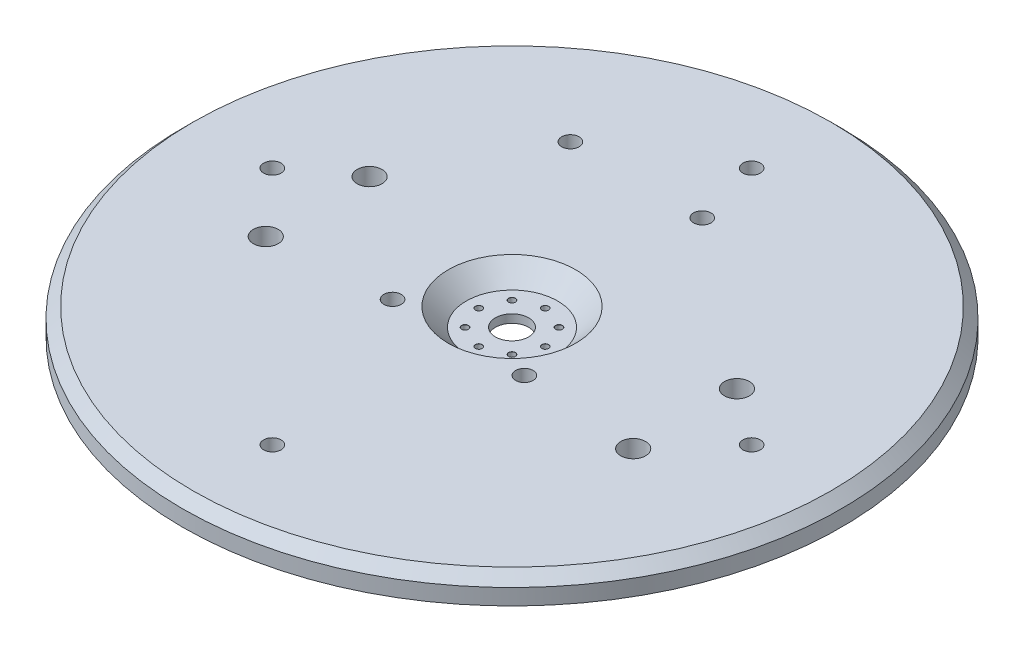
SolidWorks part; units mm, degrees
other "Markup1"
sketch "Sketch21" plane through (-65.5, -15.05, -60) normal (-0.0927, -0.2854, -0.9539) x (0.9951, -0.0609, -0.0785)
material "6061 Alloy"
ref_plane "Front Plane" through (0, 0, 0) normal (0, 0, 1) x (1, 0, 0)
ref_plane "Top Plane" through (0, 0, 0) normal (0, 1, 0) x (1, 0, 0)
ref_plane "Right Plane" through (0, 0, 0) normal (1, 0, 0) x (0, 0, -1)
sketch "Sketch1" plane through (0, 0, 0) normal (0, 1, 0) x (1, 0, 0)
  circle A0 centre (0, 0) radius 79.375
  dimension "D1" = 158.75
extrude "Boss-Extrude1" add sketch "Sketch1" along normal mid plane 6.35
sketch "Sketch2" plane through (0, -3.175, 0) normal (0, -1, 0) x (1, 0, 0)
  circle A0 centre (0, 0) radius 12.065
  circle A1 centre (0, 0) radius 79.375 construction
  dimension "D1" = 24.13
sketch "Sketch5" plane through (0, 3.175, 0) normal (0, 1, 0) x (1, 0, 0)
  circle A0 centre (0, 0) radius 10.4
  circle A1 centre (0, 0) radius 79.375 construction
  dimension "D1" = 20.8
hole_wizard "Tap Drill for M5x0.8 Tap1" positions "Sketch22" profile "Sketch23" hole size "M5x0.8" standard "ANSI Metric" end condition through all
sketch "Sketch22" plane through (0, 3.175, 0) normal (0, 1, 0) x (1, 0, 0)
  point P0 (-27.3188, 41.3898)
  point P3 (4.4312, 41.3898)
  point P6 (-15.875, -12.8959)
  point P9 (15.875, -12.8959)
  dimension "D1" = 31.75
  dimension "D2" = 41.3898
  dimension "D3" = 4.4312
  dimension "D4" = 31.75
  dimension "D5" = 12.8959
  dimension "D6" = 15.875
sketch "Sketch23" plane through (-27.3188, 3.175, -41.3898) normal (1, 0, 0) x (0, 0, 1)
  line L0 (0, 0) -> (0, 6.35)
  line L1 (0, 6.35) -> (2.1, 6.35)
  line L2 (2.1, 6.35) -> (2.1, 0)
  line L5 (2.1, 0) -> (0, 0)
  line L11 (0, -6.35) -> (0, 107.95) construction
  dimension "Thru Hole Dia." = 4.2
  dimension "Thru Hole Depth" = 6.35
hole_wizard "Tap Drill for M7x1.0 Tap1" positions "Sketch24" profile "Sketch25" hole size "M7x1.0" standard "ANSI Metric" end condition through all
sketch "Sketch24" plane through (0, 3.175, 0) normal (0, 1, 0) x (1, 0, 0)
  point P0 (-44.245, 9.9416)
  point P3 (-44.245, -15.0584)
  point P6 (44.245, 9.9416)
  point P9 (44.245, -15.0584)
  dimension "D1" = 25
  dimension "D2" = 44.245
  dimension "D3" = 9.9416
  dimension "D4" = 25
  dimension "D5" = 44.245
  dimension "D6" = 15.0584
sketch "Sketch25" plane through (-44.245, 3.175, -9.9416) normal (1, 0, 0) x (0, 0, 1)
  line L0 (0, 0) -> (0, 6.35)
  line L1 (0, 6.35) -> (3, 6.35)
  line L2 (3, 6.35) -> (3, 0)
  line L5 (3, 0) -> (0, 0)
  line L11 (0, -6.35) -> (0, 107.95) construction
  dimension "Thru Hole Dia." = 6
  dimension "Thru Hole Depth" = 6.35
sketch "Sketch28" plane through (0, 3.175, 0) normal (0, 1, 0) x (1, 0, 0)
  circle A0 centre (0, 0) radius 51
  circle A1 centre (35.8572, -36.2665) radius 4.2952
  dimension "D1" = 102
sketch "Sketch31" plane through (0, 3.175, 0) normal (0, 1, 0) x (1, 0, 0)
  line L1 (5.6569, 5.6569) -> (-5.6569, 5.6569) construction
  line L2 (5.6569, 5.6569) -> (5.6569, -5.6569) construction
  line L3 (5.6569, -5.6569) -> (-5.6569, -5.6569) construction
  line L4 (-5.6569, 5.6569) -> (-5.6569, -5.6569) construction
  line L5 (5.6569, 5.6569) -> (-5.6569, -5.6569) construction
  line L6 (5.6569, -5.6569) -> (-5.6569, 5.6569) construction
  line L7 (8, 0) -> (0, 8) construction
  line L8 (8, 0) -> (0, -8) construction
  line L9 (0, -8) -> (-8, 0) construction
  line L10 (0, 8) -> (-8, 0) construction
  line L11 (8, 0) -> (-8, 0) construction
  line L12 (0, -8) -> (0, 8) construction
  circle A0 centre (0, 0) radius 8 construction
  point P0 (0, 0)
  point P8 (0, 0)
  dimension "D1" = 16
sketch "Sketch32" plane through (0, 3.175, 0) normal (0, 1, 0) x (1, 0, 0)
  circle A0 centre (0, 0) radius 11
  circle A1 centre (0, 0) radius 4
  dimension "D1" = 22
  dimension "D2" = 8
extrude "Cut-Extrude1" cut sketch "Sketch32" against normal through all contours A1
extrude "Cut-Extrude2" cut sketch "Sketch32<4>" against normal offset from surface (4.35 mm away) 2 up to face at (0, -3.175, 4)
sketch "Sketch32<4>" plane through (0, 3.175, 0) normal (0, 1, 0) x (1, 0, 0) same geometry as "Sketch32"
chamfer "Chamfer1" distance 4.35 angle 45 1 edges at (0, 3.175, 11)
hole_wizard "Tap Drill for M2x0.4 Tap1" positions "Sketch33" profile "Sketch34" hole size "M2x0.4" standard "ANSI Metric" end condition through all
sketch "Sketch33" plane through (0, -1.175, 0) normal (0, 1, 0) x (1, 0, 0)
  point P0 (-8, 0)
  point P3 (-5.6569, 5.6569)
  point P6 (0, 8)
  point P9 (5.6569, 5.6569)
  point P12 (8, 0)
  point P15 (5.6569, -5.6569)
  point P18 (0, -8)
  point P21 (-5.6569, -5.6569)
sketch "Sketch34" plane through (-8, -1.175, 0) normal (1, 0, 0) x (0, 0, 1)
  line L0 (0, 0) -> (0, 2)
  line L1 (0, 2) -> (0.8, 2)
  line L2 (0.8, 2) -> (0.8, 0.025)
  line L3 (0.8, 0.025) -> (0.825, 0)
  line L5 (0.825, 0) -> (0, 0)
  line L6 (-0.8, 0.025) -> (-0.825, 0) construction
  line L11 (0, -6.35) -> (0, 107.95) construction
  dimension "Thru Hole Dia." = 1.6
  dimension "Thru Hole Depth" = 2
  dimension "Near C'Sink Dia." = 1.65
  dimension "Near C'Sink Angle" = 90
chamfer "Chamfer2" distance 2.5 angle 45 1 edges at (0, 3.175, 79.375)
sketch "Sketch35" plane through (0, -3.175, 0) normal (0, -1, 0) x (1, 0, 0)
  line L0 (0, 57.7234) -> (0, -57.7234) construction
  line L1 (57.7234, 0) -> (-57.7234, 0) construction
  circle A0 centre (0, 0) radius 57.7234
  dimension "D1" = 115.4468
hole_wizard "Tap Drill for M5x0.8 Tap2" positions "Sketch37" profile "Sketch38" hole size "M5x0.8" standard "ANSI Metric" end condition through all
sketch "Sketch37" plane through (0, 3.175, 0) normal (0, 1, 0) x (1, 0, 0)
  point P0 (-57.7234, 0)
  point P3 (0, 57.7234)
  point P6 (57.7234, 0)
  point P9 (0, -57.7234)
sketch "Sketch38" plane through (-57.7234, 3.175, 0) normal (1, 0, 0) x (0, 0, 1)
  line L0 (0, 0) -> (0, 6.35)
  line L1 (0, 6.35) -> (2.1, 6.35)
  line L2 (2.1, 6.35) -> (2.1, 0)
  line L5 (2.1, 0) -> (0, 0)
  line L11 (0, -6.35) -> (0, 107.95) construction
  dimension "Thru Hole Dia." = 4.2
  dimension "Thru Hole Depth" = 6.35
